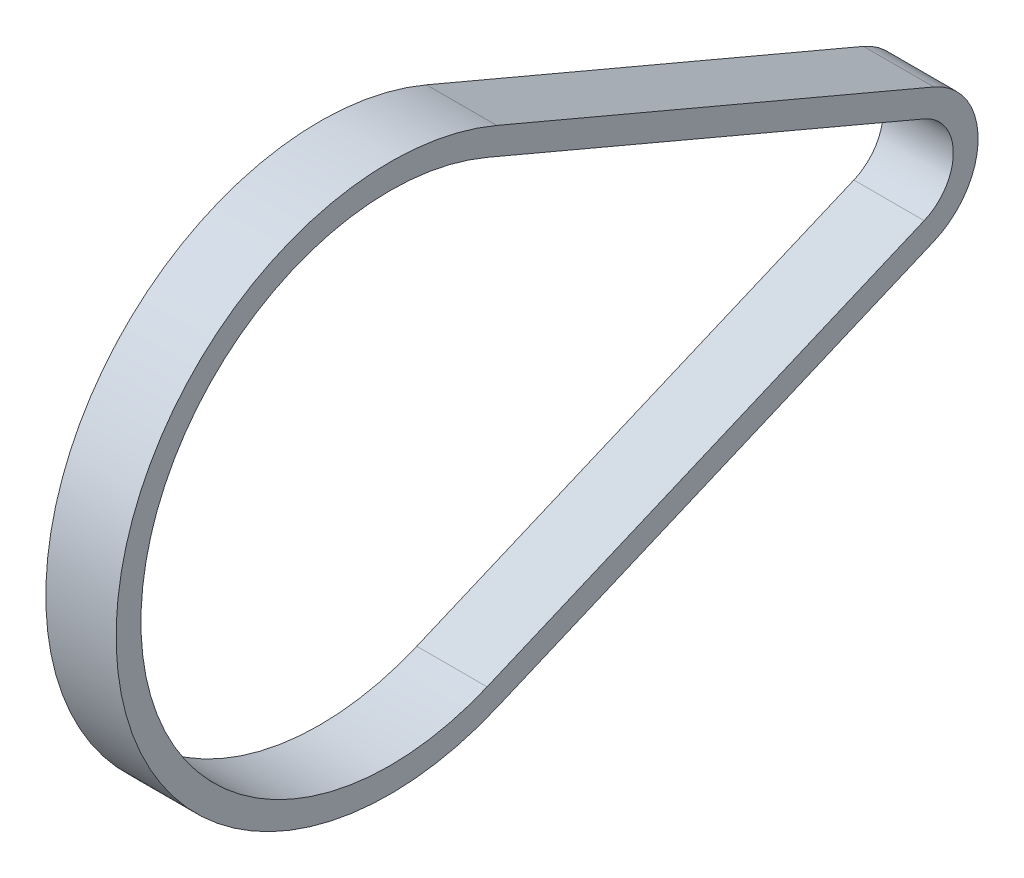
SolidWorks part; units mm, degrees
material "Zoltek Panex 33"
ref_plane "Front Plane" through (0, 0, 0) normal (0, 0, 1) x (1, 0, 0)
ref_plane "Top Plane" through (0, 0, 0) normal (0, 1, 0) x (1, 0, 0)
ref_plane "Right Plane" through (0, 0, 0) normal (1, 0, 0) x (0, 0, -1)
other "Bounding Box"
ref_plane "Default Plane" through (-8.9266, -12.7485, 0) normal (-0.1736, 0.9848, 0) x (0.9848, 0.1736, 0)
sketch "Sketch1" plane through (0, 0, 0) normal (1, 0, 0) x (0, 0, -1)
  line L0 (0, 0) -> (65.9892, 0) construction
  line L1 (12.4359, 29.3456) -> (68.3787, 5.6385)
  line L2 (12.4359, -29.3456) -> (68.3787, -5.6385)
  line L3 (13.6748, 32.269) -> (69.6175, 8.5619)
  line L4 (13.6748, -32.269) -> (69.6175, -8.5619)
  line L5 (-31.8719, 0) -> (-35.0469, 0) construction
  line L6 (72.1131, 0) -> (75.2881, 0) construction
  arc A0 (12.4359, 29.3456) -> (12.4359, -29.3456) centre (0, 0) ccw
  arc A1 (68.3787, -5.6385) -> (68.3787, 5.6385) centre (65.9892, 0) ccw
  arc A2 (13.6748, 32.269) -> (13.6748, -32.269) centre (0, 0) ccw
  arc A3 (69.6175, -8.5619) -> (69.6175, 8.5619) centre (65.9892, 0) ccw
  dimension "D2" = 3.175
  dimension "D4" = 63.7438
  dimension "D5" = 12.2479
  dimension "D1" = 65.9892
extrude "Boss-Extrude1" add sketch "Sketch1" along normal mid plane 9
